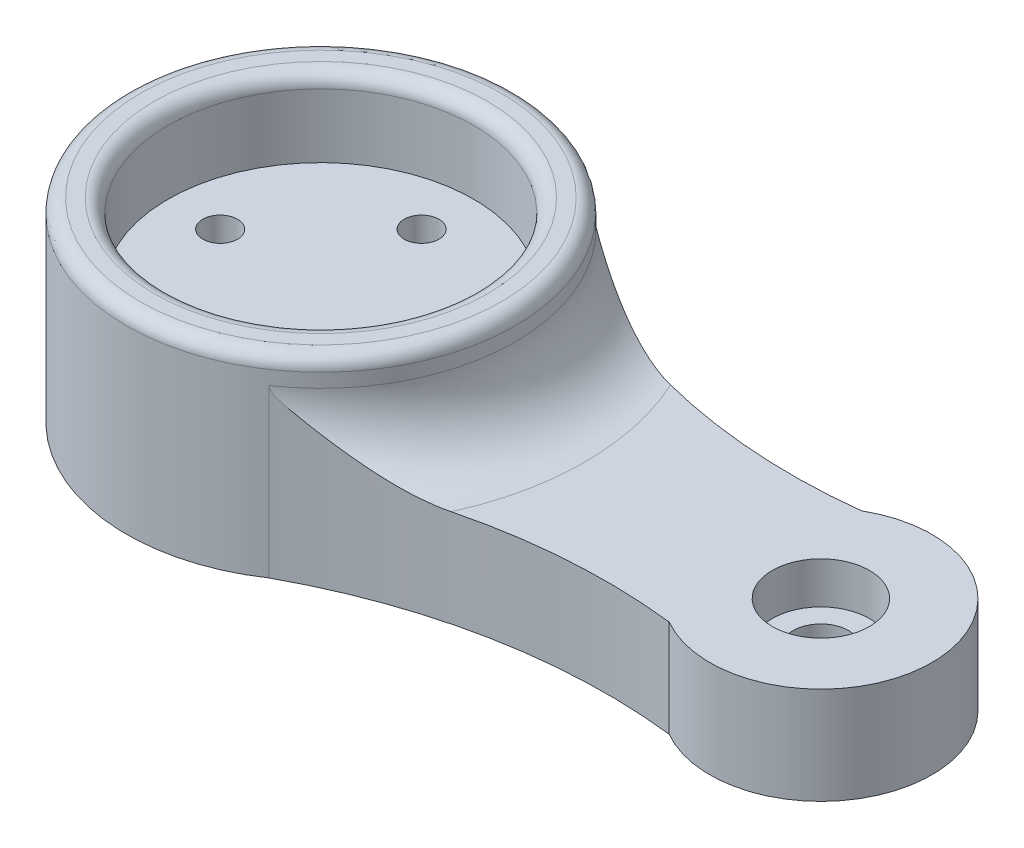
SolidWorks part; units mm, degrees
ref_plane "Ön Düzlem" through (0, 0, 0) normal (0, 0, 1) x (1, 0, 0)
ref_plane "Üst Düzlem" through (0, 0, 0) normal (0, 1, 0) x (1, 0, 0)
ref_plane "Sağ Düzlem" through (0, 0, 0) normal (1, 0, 0) x (0, 0, -1)
sketch "Sketch1" plane through (0, 0, 0) normal (0, 1, 0) x (1, 0, 0)
  line L0 (0, 0) -> (63.8182, 0) construction
  circle A0 centre (0, 0) radius 14
  circle A1 centre (36, 0) radius 8
  circle A2 centre (36, 0) radius 2
  arc A3 (7.8499, 11.5922) -> (32.0022, 6.9295) centre (27.2681, 47.2917) ccw
  arc A4 (7.8499, -11.5922) -> (32.0022, -6.9295) centre (27.2681, -47.2917) cw
  dimension "D1" = 4
  dimension "D2" = 16
  dimension "D3" = 28
  dimension "D4" = 36
extrude "Boss-Extrude1" add sketch "Sketch1" along normal blind 14 contours A0 region at (0, 0, 0)
extrude "Boss-Extrude2" add sketch "Sketch1<3>" along normal blind 7 contours A1 L0 A2 | L0 A1 A2 | A0 L0 A1 A3 | L0 A0 A4 A1 region at (36, 0, -3.5651) region at (36, 0, 3.5651) region at (20.3489, 0, -4.171) region at (20.3489, 0, 4.171)
sketch "Sketch1<3>" plane through (0, 0, 0) normal (0, 1, 0) x (1, 0, 0) same geometry as "Sketch1"
fillet "Fillet3" radius 5 1 edges at (14, 7, 0)
sketch "Sketch2" plane through (0, 7, 0) normal (0, 1, 0) x (1, 0, 0)
  circle A0 centre (36, 0) radius 2 construction
  circle A1 centre (36, 0) radius 2
  circle A2 centre (36, 0) radius 3.5
  dimension "D1" = 7
sketch "Sketch3" plane through (0, 14, 0) normal (0, 1, 0) x (1, 0, 0)
  circle A0 centre (0, 0) radius 11
extrude "Cut-Extrude2" cut sketch "Sketch3" against normal blind 5.6
sketch "Sketch4" plane through (0, 8.4, 0) normal (0, 1, 0) x (1, 0, 0)
  circle A1 centre (0, 7.25) radius 1.25
  circle A2 centre (7.25, 0) radius 1.25
  circle A3 centre (0, -7.25) radius 1.25
  circle A4 centre (-7.25, 0) radius 1.25
  dimension "D1" = 2.5
  dimension "D2" = 7.25
  dimension "D3" = 4
extrude "Cut-Extrude3" cut sketch "Sketch4" against normal blind 14.6
fillet "Fillet4" radius 1 2 edges at (0, 14, 11) (0, 14, 14)
sketch "Sketch5" plane through (0, 0, 0) normal (0, -1, 0) x (1, 0, 0)
  circle A0 centre (36, 0) radius 3.5
sketch "Sketch6" plane through (0, 0, 0) normal (0, -1, 0) x (1, 0, 0)
  circle A0 centre (36, 0) radius 3.5
sketch "Sketch7" plane through (0, 7, 0) normal (0, 1, 0) x (1, 0, 0)
  circle A0 centre (36, 0) radius 3.5
extrude "Cut-Extrude4" cut sketch "Sketch7" against normal blind 3
